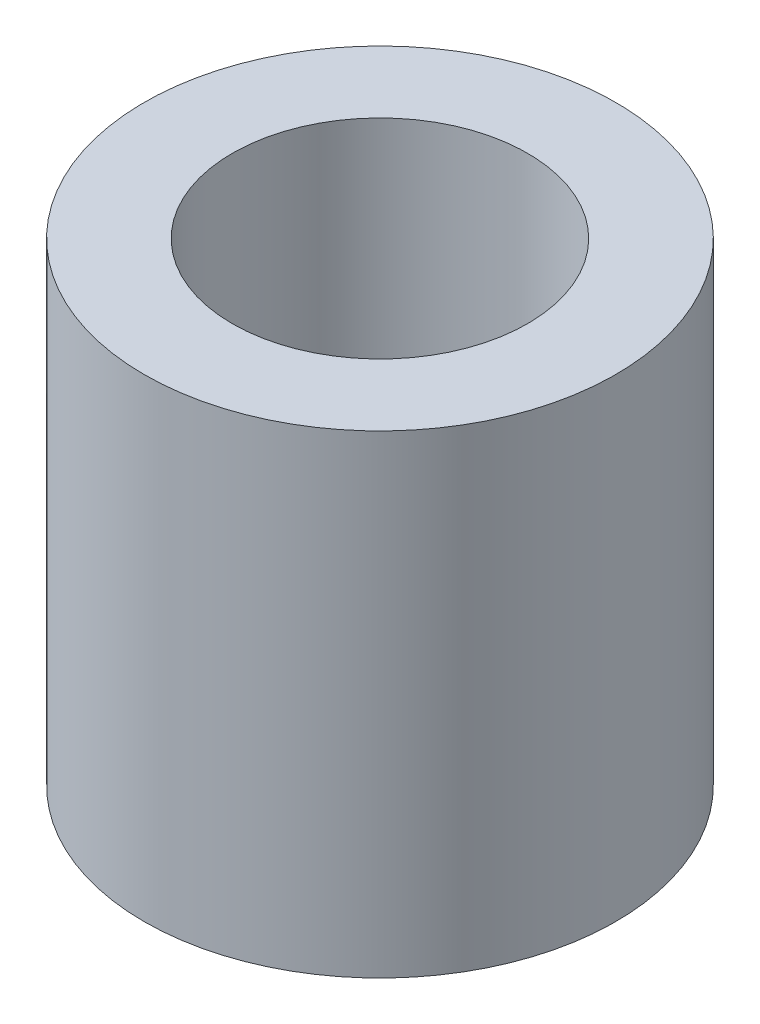
SolidWorks part; units mm, degrees
ref_plane "Front Plane" through (0, 0, 0) normal (0, 0, 1) x (1, 0, 0)
ref_plane "Top Plane" through (0, 0, 0) normal (0, 1, 0) x (1, 0, 0)
ref_plane "Right Plane" through (0, 0, 0) normal (1, 0, 0) x (0, 0, -1)
sketch "Sketch1" plane through (0, 0, 0) normal (0, 1, 0) x (1, 0, 0)
  circle A0 centre (0, 0) radius 12.5
  dimension "SLEEVE_OD" = 25
extrude "Boss-Extrude1" add sketch "Sketch1" along normal blind 25.1241
sketch "Sketch2" plane through (0, 0, 0) normal (0, 1, 0) x (1, 0, 0)
  circle A0 centre (0, 0) radius 7.8282
  dimension "BORE_D" = 15.6565
extrude "Cut-Extrude1" cut sketch "Sketch2" along normal through all
chamfer "Chamfer1" distance 2.3403 angle 60 rebuild error yes
